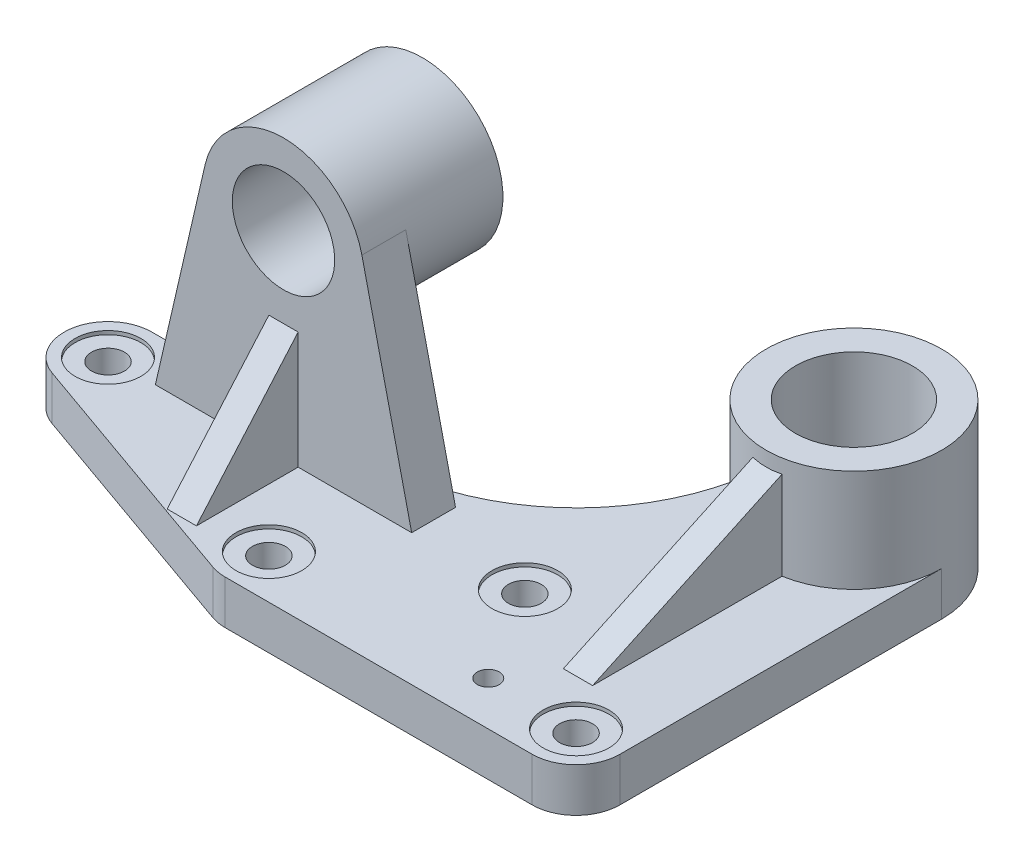
SolidWorks part; units mm, degrees
ref_plane "Front Plane" through (0, 0, 0) normal (0, 0, 1) x (1, 0, 0)
ref_plane "Top Plane" through (0, 0, 0) normal (0, 1, 0) x (1, 0, 0)
ref_plane "Right Plane" through (0, 0, 0) normal (1, 0, 0) x (0, 0, -1)
sketch "Sketch2" plane through (0, 0, 0) normal (0, 1, 0) x (1, 0, 0)
  line L0 (38.1, 0) -> (38.1, -139.7)
  line L1 (19.05, -158.75) -> (-114.3, -158.75)
  line L2 (-228.5902, -119.564) -> (-120.6402, -157.664)
  line L3 (-222.25, -82.55) -> (-126.8412, -82.55)
  circle A0 centre (0, 0) radius 38.1
  arc A1 (19.05, -158.75) -> (38.1, -139.7) centre (19.05, -139.7) ccw
  arc A2 (-120.6402, -157.664) -> (-114.3, -158.75) centre (-114.3, -139.7) ccw
  arc A3 (-222.25, -82.55) -> (-228.5902, -119.564) centre (-222.25, -101.6) ccw
  arc A4 (-126.8412, -82.55) -> (-38.0523, 1.905) centre (-126.8412, 6.35) ccw
  circle A5 centre (-222.25, -101.6) radius 14.2875
  circle A6 centre (-114.3, -139.7) radius 14.2875
  circle A7 centre (19.05, -139.7) radius 14.2875
  circle A8 centre (-44.45, -98.425) radius 14.2875
  circle A9 centre (-222.25, -101.6) radius 7.1438
  circle A10 centre (-114.3, -139.7) radius 7.1437
  circle A11 centre (-44.45, -98.425) radius 7.1437
  circle A12 centre (19.05, -139.7) radius 7.1437
  circle A13 centre (0, 0) radius 25.4
  circle A14 centre (-19.05, -139.7) radius 4.7625
  dimension "D1" = 76.2
  dimension "D3" = 38.1
  dimension "D5" = 38.1
  dimension "D8" = 38.1
  dimension "D10" = 177.8
  dimension "D11" = 28.575
  dimension "D14" = 14.2875
  dimension "D15" = 50.8
  dimension "D16" = 9.525
  dimension "D2" = 139.7
  dimension "D4" = 133.35
  dimension "D6" = 38.1
  dimension "D7" = 241.3
  dimension "D9" = 133.35
  dimension "D12" = 69.85
  dimension "D13" = 41.275
  dimension "D17" = 25.4
extrude "Boss-Extrude1" add sketch "Sketch2" along normal blind 17.4625 contours A0 A13 | A4 L3 A3 L2 A2 L1 A1 L0 A0 A8 A7 A6 A5 | A6 A10 | A8 A11 | A7 A12 | A5 A9 region at (-0.9258, 0, 37.0108) region at (-68.1785, 0, 101.0289) region at (-236.1334, 0, 101.6) region at (-128.1834, 0, 139.7) region at (5.1666, 0, 139.7) region at (-58.3334, 0, 98.425)
extrude "Boss-Extrude2" add sketch "Sketch2<4>" along normal blind 19.05 contours A4 L3 A3 L2 A2 L1 A1 L0 A0 A8 A7 A6 A5 | A0 A13 region at (-0.9258, 0, 37.0108) region at (-68.1785, 0, 101.0289)
sketch "Sketch2<4>" plane through (0, 0, 0) normal (0, 1, 0) x (1, 0, 0) same geometry as "Sketch2"
extrude "Boss-Extrude3" add sketch "Sketch2<5>" along normal blind 63.5 contours A0 A13 region at (-0.9258, 0, 37.0108)
sketch "Sketch2<5>" plane through (0, 0, 0) normal (0, 1, 0) x (1, 0, 0) same geometry as "Sketch2"
sketch "Sketch4" plane through (0, 0, 82.55) normal (0, 0, -1) x (-1, 0, 0)
  line L0 (25.4, 63.5) -> (-25.4, 63.5) construction
  line L1 (180.0799, 112.6314) -> (201.6848, 19.05)
  line L2 (228.5902, 19.05) -> (120.6402, 19.05) construction
  line L3 (112.0201, 112.6314) -> (90.4152, 19.05)
  line L4 (-19.05, 19.05) -> (114.3, 19.05) construction
  line L5 (201.6848, 19.05) -> (90.4152, 19.05)
  circle A0 centre (146.05, 104.775) radius 34.925
  circle A1 centre (146.05, 104.775) radius 22.225
  line M5 (222.25, 19.05) -> (126.8412, 19.05)
  dimension "D2" = 69.85
  dimension "D3" = 44.45
  dimension "D1" = 41.275
  dimension "D4" = 146.05
  dimension "D5" = 77
  dimension "D6" = 77
extrude "Boss-Extrude4" add sketch "Sketch4" against normal blind 19.05 contours A0 L3 L5 L1 M5 | A0 A1 region at (-146.05, 48.8036, 82.55) region at (-179.769, 108.6168, 82.55)
extrude "Boss-Extrude5" add sketch "Sketch4<5>" along normal blind 41.275 contours A0 A1 region at (-179.769, 108.6168, 82.55)
sketch "Sketch4<5>" plane through (0, 0, 82.55) normal (0, 0, -1) x (-1, 0, 0) same geometry as "Sketch4"
sketch "Sketch5" plane through (0, 0, 0) normal (1, 0, 0) x (0, 0, -1)
  line L0 (-38.1, 57.15) -> (-119.8057, 19.05)
  line L1 (-101.6, 19.05) -> (-82.55, 19.05) construction
  line L2 (0, 19.05) -> (-139.7, 19.05) construction
  line L3 (-38.1, 63.5) -> (-38.1, 19.05) construction
  dimension "D1" = 25
  dimension "D2" = 38.1
rib "Rib1" sketch "Sketch5" sketch "Sketch5" thickness 12.7 extrusion direction parallel to sketch draft on no parameters "D1"=12.7
ref_plane "Plane1" through (-146.05, 0, 0) normal (1, 0, 0) x (0, 0, -1)
sketch "Sketch6" plane through (-146.05, 0, 0) normal (1, 0, 0) x (0, 0, -1)
  line L0 (-145.7598, 19.05) -> (-101.6, 69.85)
  line L1 (0, 19.05) -> (-139.7, 19.05) construction
  line L2 (-101.6, 112.6314) -> (-101.6, 19.05) construction
  dimension "D1" = 49
  dimension "D2" = 69.85
rib "Rib2" sketch "Sketch6" sketch "Sketch6" thickness 12.7 extrusion direction parallel to sketch draft on no parameters "D1"=12.7
sketch "Sketch7" plane through (-146.05, 0, 0) normal (1, 0, 0) x (0, 0, -1)
  line L0 (-82.55, 19.05) -> (-59.0873, 69.85)
  line L1 (-82.55, 112.6314) -> (-82.55, 19.05) construction
  line L2 (-82.55, 69.85) -> (-41.275, 69.85) construction
  line L3 (-82.55, 69.85) -> (-82.55, 112.6314) construction
  point P6 (-82.55, 91.2407)
  dimension "D1" = 31.75
rib "Rib3" sketch "Sketch7" sketch "Sketch7" thickness 12.7 extrusion direction parallel to sketch draft on no parameters "D1"=12.7
